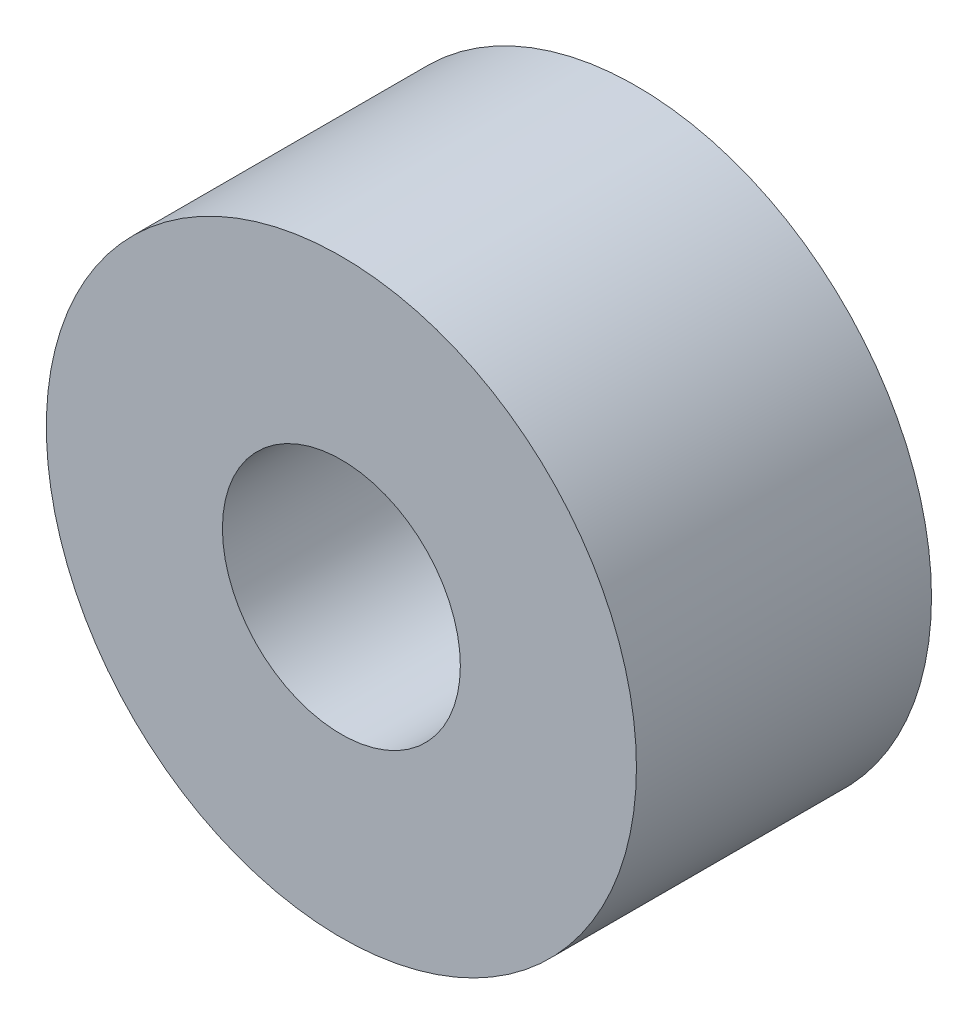
SolidWorks part; units mm, degrees
ref_plane "Front Plane" through (0, 0, 0) normal (0, 0, 1) x (1, 0, 0)
ref_plane "Top Plane" through (0, 0, 0) normal (0, 1, 0) x (1, 0, 0)
ref_plane "Right Plane" through (0, 0, 0) normal (1, 0, 0) x (0, 0, -1)
sketch "Sketch1" plane through (0, 0, 0) normal (1, 0, 0) x (0, 0, -1)
  line L0 (-3.9688, -3.2004) -> (-3.9688, 3.2004) construction
  line L1 (3.9688, -7.9375) -> (-3.9688, -7.9375) construction
  line L2 (3.9688, -7.9375) -> (3.9688, 7.9375) construction
  line L3 (3.9688, 7.9375) -> (-3.9688, 7.9375) construction
  line L4 (-3.9688, -7.9375) -> (-3.9688, 7.9375) construction
  line L5 (0, 7.9375) -> (0, -7.9375) construction
  line L6 (3.9688, 0) -> (-3.9688, 0) construction
  point P0 (0, 0)
  point P7 (-3.9688, 0)
  dimension "D1" = 6.4008
  dimension "D2" = 15.875
sketch "Sketch3" plane through (0, 0, 0) normal (0, 0, 1) x (1, 0, 0)
  circle A0 centre (0, 0) radius 3.2004 construction
  circle A1 centre (0, 0) radius 7.9375 construction
  point P6 (0, -3.2004)
  dimension "OD" = 15.875
  dimension "ID" = 6.4008
sketch "Sketch2" plane through (0, 0, 0) normal (0, 0, 1) x (1, 0, 0)
  circle A0 centre (0, 0) radius 7.9375
  circle A1 centre (0, 0) radius 3.2004
extrude "Extrude1" add sketch "Sketch2" along normal up to vertex and the other way up to vertex up to point (0, -7.9375, 3.9688) other way up to point (0, 7.9375, -3.9688)
ref_plane "Plane1" through (0, 0, -3.9688) normal (0, 0, -1) x (-1, 0, 0)
equation "\"D1@Sketch1\"=\"ID@Sketch3\""
equation "\"D2@Sketch1\"=\"OD@Sketch3\""
